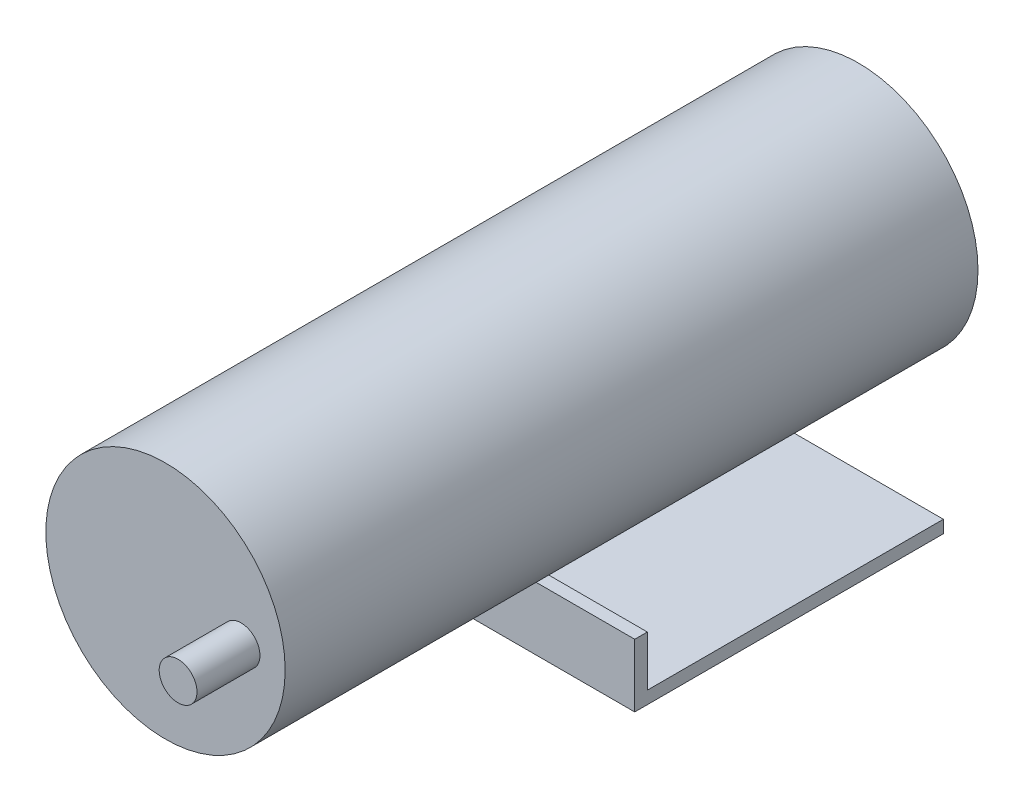
SolidWorks part; units mm, degrees
ref_plane "Plan de face" through (0, 0, 0) normal (0, 0, 1) x (1, 0, 0)
ref_plane "Plan de dessus" through (0, 0, 0) normal (0, 1, 0) x (1, 0, 0)
ref_plane "Plan de droite" through (0, 0, 0) normal (1, 0, 0) x (0, 0, -1)
sketch "Esquisse1" plane through (0, 0, 0) normal (0, 0, 1) x (1, 0, 0)
  circle A0 centre (0, 0) radius 19
  dimension "D1" = 38
extrude "Boss.-Extru.1" add sketch "Esquisse1" along normal blind 110
sketch "Esquisse2" plane through (0, 0, 110) normal (0, 0, 1) x (1, 0, 0)
  circle A0 centre (12, 0) radius 3
  dimension "D1" = 12
  dimension "D3" = 0
  dimension "D2" = 6
extrude "Boss.-Extru.2" add sketch "Esquisse2" along normal blind 10
sketch "Esquisse3" plane through (0, 0, 0) normal (1, 0, 0) x (0, 0, -1)
  line L0 (-59, -19) -> (-59, -29)
  line L1 (-110, -19) -> (0, -19) construction
  line L2 (-59, -29) -> (-10, -29)
  line L3 (-10, -29) -> (-10, -27)
  line L4 (-10, -27) -> (-57, -27)
  line L5 (-57, -27) -> (-57, -19)
  line L6 (-59, -19) -> (-57, -19)
  line L8 (0, -19) -> (0, 19) construction
  dimension "D1" = 10
  dimension "D2" = 49
  dimension "D3" = 10
  dimension "D4" = 2
  dimension "D5" = 2
extrude "Boss.-Extru.3" add sketch "Esquisse3" against normal blind 23.5 and the other way blind 23.5 separate body
sketch3d "Esquisse3D3" plane through (0, 0, 0) normal (0, 0, 1) x (1, 0, 0)
equation "\"22.5.00mm\"=47"
